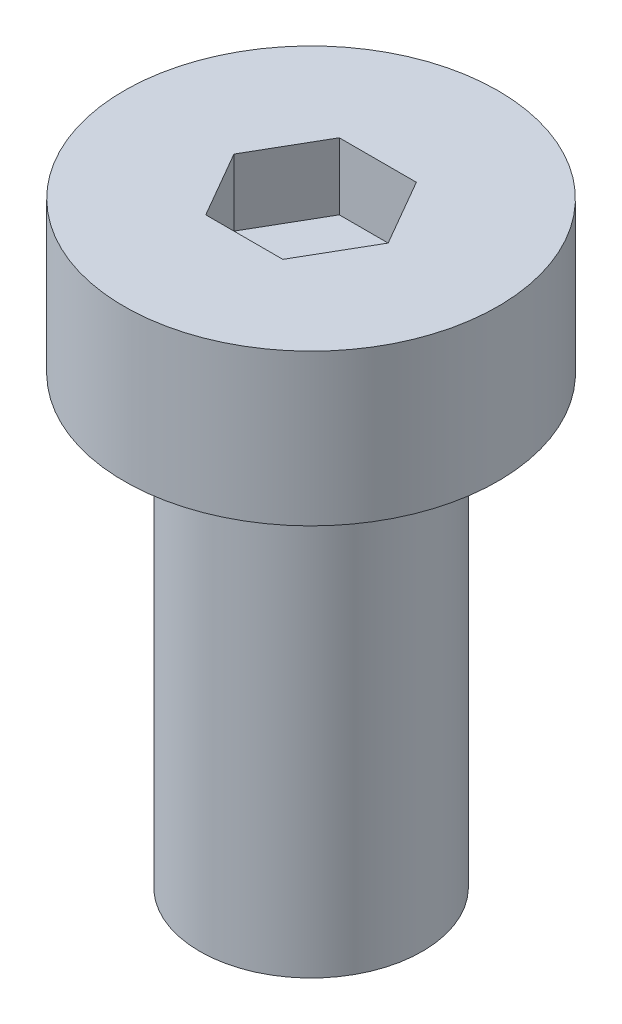
SolidWorks part; units mm, degrees
ref_plane "Front Plane" through (0, 0, 0) normal (0, 0, 1) x (1, 0, 0)
ref_plane "Top Plane" through (0, 0, 0) normal (0, 1, 0) x (1, 0, 0)
ref_plane "Right Plane" through (0, 0, 0) normal (1, 0, 0) x (0, 0, -1)
sketch "Sketch1" plane through (0, 0, 0) normal (0, 1, 0) x (1, 0, 0)
  circle A0 centre (0, 0) radius 2.5
  dimension "D1" = 5
extrude "Boss-Extrude1" add sketch "Sketch1" along normal blind 10
sketch "Sketch3" plane through (0, 0, 0) normal (0, 0, 1) x (1, 0, 0)
  line L0 (2.5, 10) -> (-2.5, 10) construction
  line L2 (0, 10) -> (0, 13.4)
  line L3 (-4.2, 10) -> (0, 10)
  line L6 (-4.2, 10) -> (-4.2, 13.4)
  line L7 (-4.2, 13.4) -> (0, 13.4)
  dimension "D1" = 3.4
  dimension "D2" = 4.2
revolve "Revolve2" add sketch "Sketch3" angle 360 about L2
sketch "Sketch4" plane through (0, 13.4, 0) normal (0, 1, 0) x (1, 0, 0)
  line L1 (1.7321, 0) -> (0.866, 1.5)
  line L2 (0.866, 1.5) -> (-0.866, 1.5)
  line L3 (-0.866, 1.5) -> (-1.7321, 0)
  line L4 (-1.7321, 0) -> (-0.866, -1.5)
  line L5 (-0.866, -1.5) -> (0.866, -1.5)
  line L6 (0.866, -1.5) -> (1.7321, 0)
  circle A0 centre (0, 0) radius 1.5 construction
  dimension "D1" = 3
extrude "Cut-Extrude1" cut sketch "Sketch4" against normal blind 1.5
fillet "Fillet1" radius 1 rebuild error yes type face fillet
fillet "Fillet2" radius 1 rebuild error yes type face fillet
fillet "Fillet3" radius 1 rebuild error yes type face fillet
fillet "Fillet4" radius 1 rebuild error yes type face fillet
